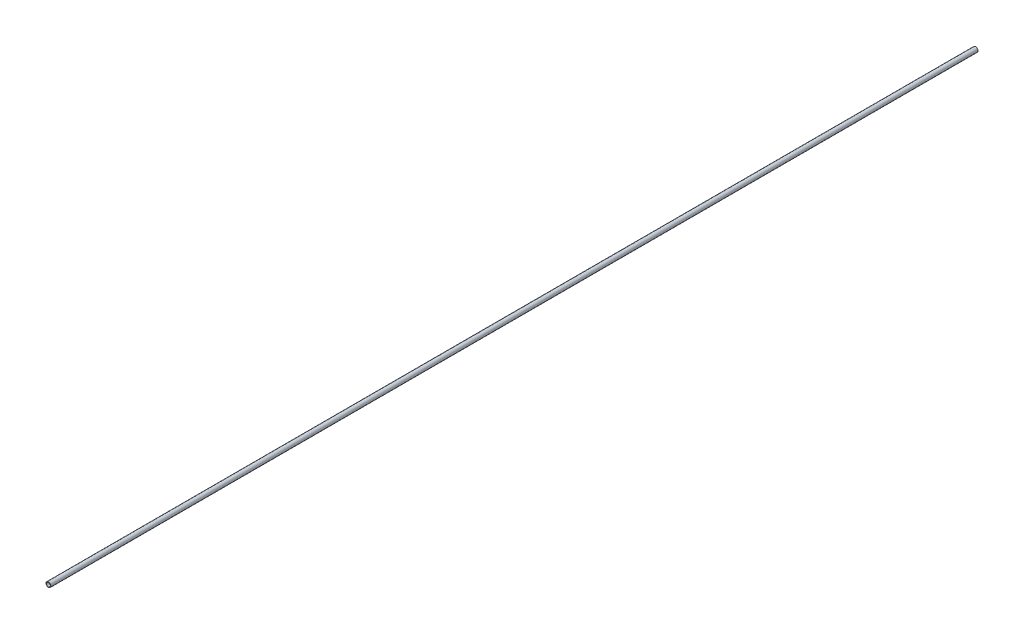
SolidWorks part; units mm, degrees
material "Plain Carbon Steel"
ref_plane "Plane1" through (0, 0, 0) normal (0, 0, 1) x (1, 0, 0)
ref_plane "Plane2" through (0, 0, 0) normal (0, 1, 0) x (1, 0, 0)
ref_plane "Plane3" through (0, 0, 0) normal (1, 0, 0) x (0, 0, -1)
sketch "Sketch1" plane through (0, 0, 0) normal (0, 0, 1) x (1, 0, 0)
  circle A0 centre (0, 0) radius 13.3223
  circle A1 centre (0, 0) radius 16.7005
extrude "BasePipe" add sketch "Sketch1" along normal mid plane 6426.2
sketch "Sketch10" plane through (0, 0, 0) normal (1, 0, 0) x (0, 0, -1)
  line L0 (-3048.5857, 0) -> (-3090.2803, 0) construction
  line L1 (3213.1, 16.7005) -> (-3213.1, 16.7005) construction
  line L2 (-3213.1, 16.7005) -> (-3213.1, -16.7005) construction
  point P2 (-3190.875, 16.7005)
  dimension "D1" = 22.225
ref_plane "Plane4" through (0, 0, 3190.875) normal (0, 0, 1) x (1, 0, 0)
sketch "Sketch11" plane through (0, 0, 3190.875) normal (0, 0, 1) x (1, 0, 0)
  circle A0 centre (0, 0) radius 16.7005 construction
  circle A1 centre (0, 0) radius 16.7005
curve "Helix/Spiral2" pitch 2.2087 height 22.087 turns 10
sketch "Sketch14" plane through (0, 0, 0) normal (1, 0, 0) x (0, 0, -1)
  line L0 (0, -6.1404) -> (2.317, -2.1272)
  line L1 (2.317, -2.1272) -> (2.317, 6.1404)
  line L2 (2.317, 6.1404) -> (-2.317, 6.1404)
  line L3 (0, -6.1404) -> (-2.317, -2.1272)
  line L4 (-2.317, -2.1272) -> (-2.317, 6.1404)
  line L5 (2.317, -6.1404) -> (2.317, -2.1272) construction
  line L6 (2.317, -6.1404) -> (0, -6.1404) construction
  line L7 (-3047.862, 10.5601) -> (-3045.5449, 14.5733)
  line L8 (-3045.5449, 14.5733) -> (-3045.5449, 23.2351)
  line L9 (-3045.5449, 23.2351) -> (-3050.179, 23.2351)
  line L10 (-3047.862, 10.5601) -> (-3050.179, 14.5733)
  line L11 (-3050.179, 14.5733) -> (-3050.179, 23.2351)
  line L12 (-3045.5449, 10.5601) -> (-3045.5449, 14.5733) construction
  line L13 (-3045.5449, 10.5601) -> (-3047.862, 10.5601) construction
  line L14 (-3050.179, 14.5733) -> (-3045.5449, 14.5733) construction
  line L15 (-3047.862, 10.5601) -> (-3047.862, 14.5733) construction
  point P6 (0, 6.1404)
  point P13 (-3047.862, 23.2351)
